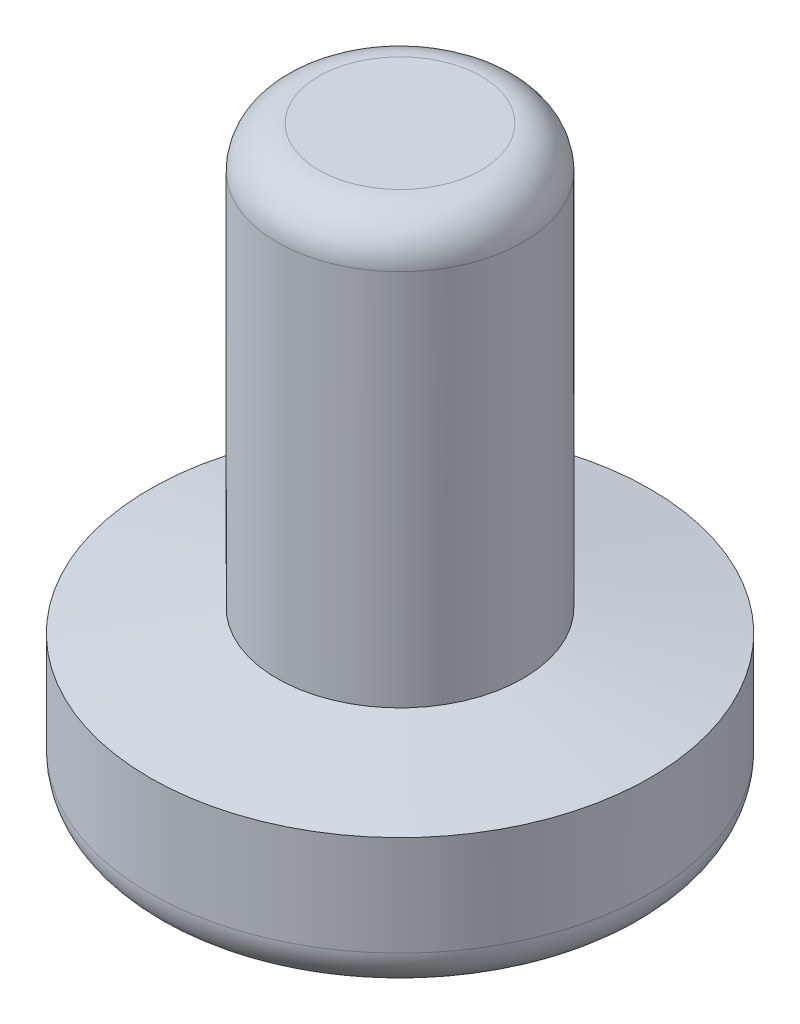
SolidWorks part; units mm, degrees
ref_plane "Alzado" through (0, 0, 0) normal (0, 0, 1) x (1, 0, 0)
ref_plane "Planta" through (0, 0, 0) normal (0, 1, 0) x (1, 0, 0)
ref_plane "Vista lateral" through (0, 0, 0) normal (1, 0, 0) x (0, 0, -1)
sketch "Croquis1" plane through (0, 0, 0) normal (0, 1, 0) x (1, 0, 0)
  circle A0 centre (0, 0) radius 3
  dimension "D1" = 6
extrude "Saliente-Extruir1" add sketch "Croquis1" along normal blind 2
sketch "Croquis2" plane through (0, 2, 0) normal (0, 1, 0) x (1, 0, 0)
  circle A0 centre (0, 0) radius 1.475
  dimension "D1" = 2.95
extrude "Saliente-Extruir2" add sketch "Croquis2" along normal blind 5
chamfer "Chaflán1" distance 0.3 angle 80 1 edges at (0, 2, 3) first distance on face at (0, 2, 3)
fillet "Redondeo1" radius 0.5 1 edges at (0, 7, 1.475)
fillet "Redondeo2" radius 0.5 1 edges at (0, 0, 3)
